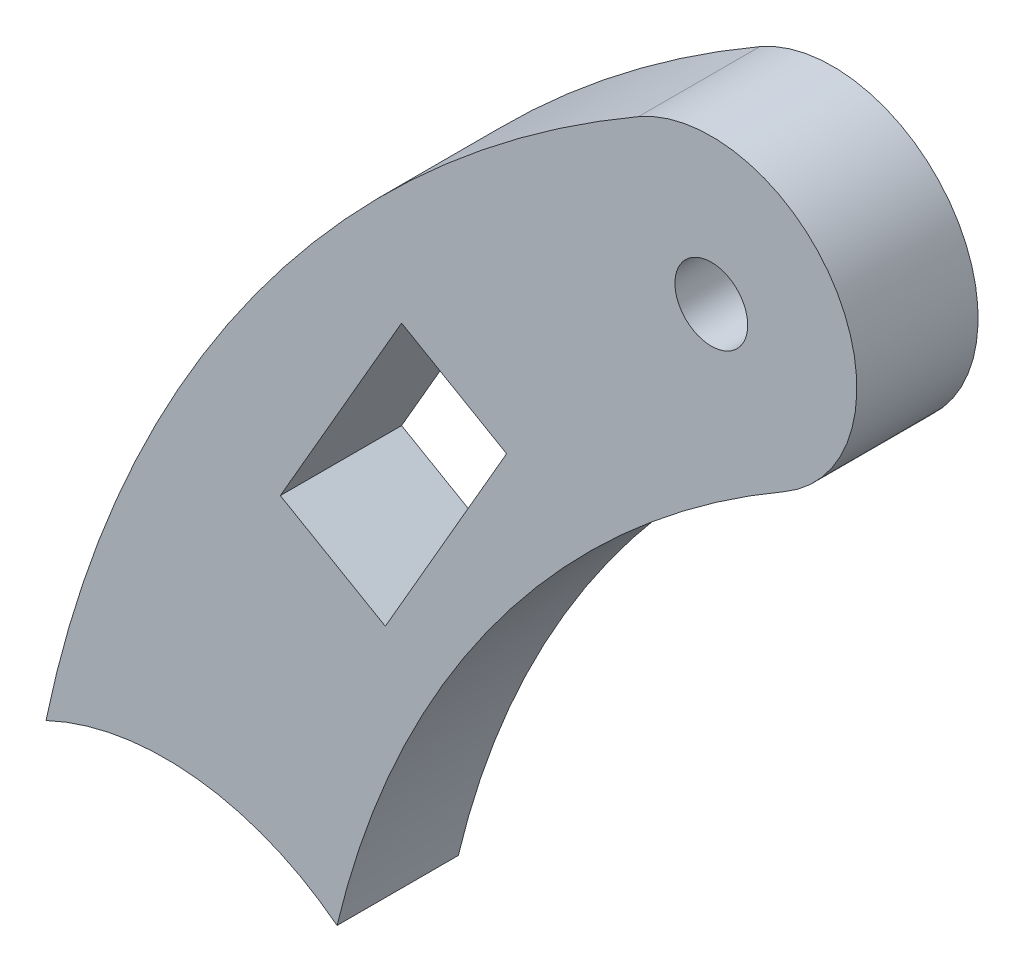
SolidWorks part; units mm, degrees
ref_plane "Plan de face" through (0, 0, 0) normal (0, 0, 1) x (1, 0, 0)
ref_plane "Plan de dessus" through (0, 0, 0) normal (0, 1, 0) x (1, 0, 0)
ref_plane "Plan de droite" through (0, 0, 0) normal (1, 0, 0) x (0, 0, -1)
sketch "Esquisse1" plane through (0, 0, 0) normal (0, 0, 1) x (1, 0, 0)
  line L0 (-22.5, 38.9711) -> (0, 0) construction
  line L1 (0, 0) -> (-45, 0) construction
  line L2 (-46.4244, 7.5905) -> (-29.8397, 36.3162) construction
  line L3 (0, 0) -> (-38.9711, 22.5) construction
  line L4 (-40.2702, 23.25) -> (-35.9401, 20.75)
  line L5 (-35.9401, 20.75) -> (-30.9401, 29.4103)
  line L6 (-30.9401, 29.4103) -> (-35.2702, 31.9103)
  line L7 (-35.2702, 31.9103) -> (-40.2702, 23.25)
  arc A0 (-45, 0) -> (-22.5, 38.9711) centre (0, 0) cw construction
  arc A1 (-25.5, 44.1673) -> (-49.9306, 10.3894) centre (0, 0) ccw
  arc A2 (-19.5, 33.775) -> (-37.9306, 9.0704) centre (0, 0) ccw
  arc A3 (-19.5, 33.775) -> (-25.5, 44.1673) centre (-22.5, 38.9711) ccw
  arc A4 (-49.9306, 10.3894) -> (-37.9306, 9.0704) centre (-45, 0) cw
  circle A5 centre (-22.5, 38.9711) radius 1.5
  circle A6 centre (-45, 0) radius 1.5 construction
  circle A7 centre (-45, 0) radius 11.5 construction
  dimension "D1" = 45
  dimension "D2" = 3
  dimension "D3" = 6
  dimension "D4" = 45
  dimension "D6" = 23
  dimension "D7" = 51
  dimension "D8" = 39
  dimension "D5" = 1
  dimension "D9" = 0
  dimension "D10" = 10
  dimension "D11" = 5
extrude "Boss.-Extru.1" add sketch "Esquisse1" along normal blind 5
